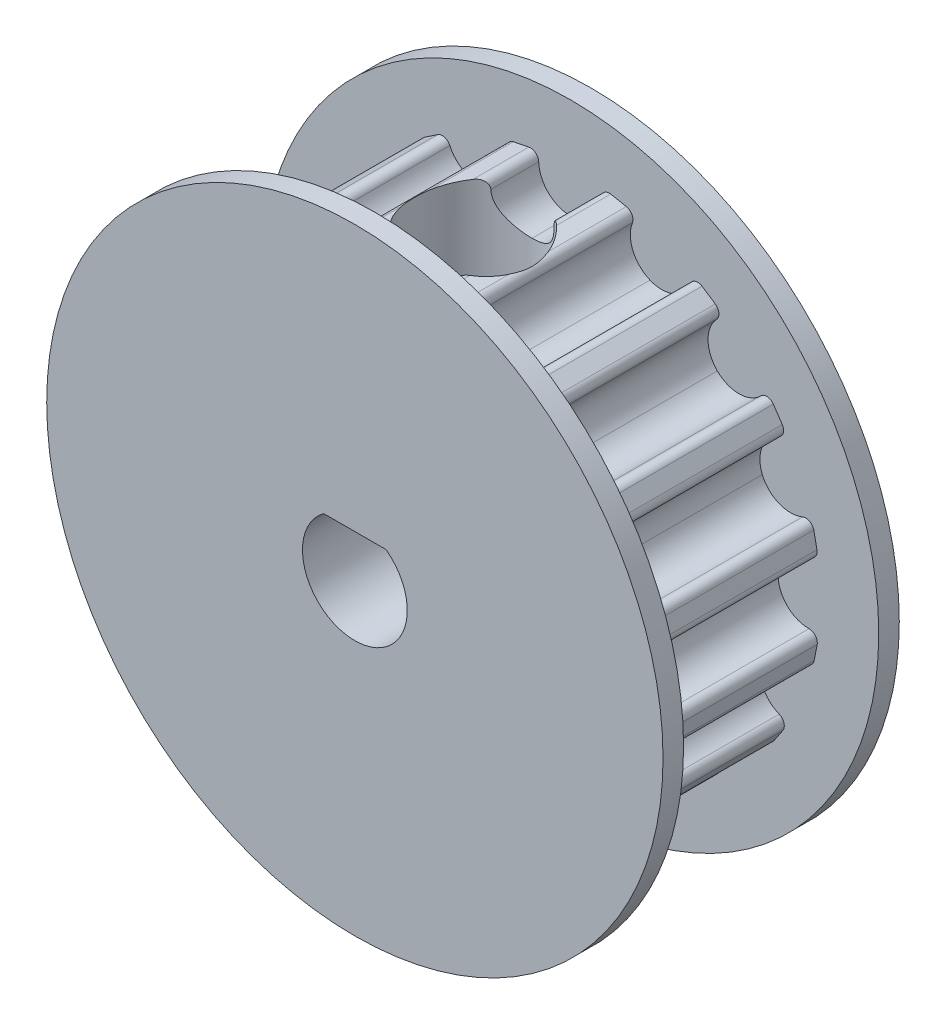
SolidWorks part; units mm, degrees
ref_plane "Front Plane" through (0, 0, 0) normal (1, 0, 0) x (0, 1, 0)
ref_plane "Top Plane" through (0, 0, 0) normal (0, 0, 1) x (0, 1, 0)
ref_plane "Right Plane" through (0, 0, 0) normal (0, 1, 0) x (-1, 0, 0)
sketch "Pulley Profile" plane through (0, 0, 0) normal (0, 0, 1) x (0, 1, 0)
  line L0 (0, 0) -> (0, 160.2939) construction
  line L1 (0, 0) -> (61.3418, 148.0922) construction
  line L2 (1.9542, 12.0044) -> (2.7129, 11.856)
  line L3 (1.8899, 11.6096) -> (2.6361, 11.4636) construction
  line L4 (6.3993, 10.3428) -> (7.0435, 9.9153)
  line L5 (9.8702, 7.1066) -> (10.3017, 6.4651)
  line L6 (11.8384, 2.7884) -> (11.9917, 2.0307)
  line L7 (12.0044, -1.9542) -> (11.856, -2.7129)
  line L8 (10.3428, -6.3993) -> (9.9153, -7.0435)
  line L9 (7.1066, -9.8702) -> (6.4651, -10.3017)
  line L10 (2.7884, -11.8384) -> (2.0307, -11.9917)
  line L11 (-1.9542, -12.0044) -> (-2.7129, -11.856)
  line L12 (-6.3993, -10.3428) -> (-7.0435, -9.9153)
  line L13 (-9.8702, -7.1066) -> (-10.3017, -6.4651)
  line L14 (-11.8384, -2.7884) -> (-11.9917, -2.0307)
  line L15 (-12.0044, 1.9542) -> (-11.856, 2.7129)
  line L16 (-10.3428, 6.3993) -> (-9.9153, 7.0435)
  line L17 (-7.1066, 9.8702) -> (-6.4651, 10.3017)
  line L18 (-2.7884, 11.8384) -> (-2.0307, 11.9917)
  circle A0 centre (0, 0) radius 10.1024 construction
  circle A1 centre (0, 0) radius 12.1624 construction
  arc A6 (0, 10.1024) -> (1.4899, 11.6059) centre (0, 11.5924) ccw
  arc A7 (1.4899, 11.6059) -> (1.9542, 12.0044) centre (1.8899, 11.6096) cw
  arc A8 (2.7129, 11.856) -> (3.0097, 11.3211) centre (2.6361, 11.4636) cw
  arc A9 (3.0097, 11.3211) -> (3.866, 9.3334) centre (4.4601, 10.7677) ccw
  circle A10 centre (0, 0) radius 12.7324 construction
  arc A11 (3.866, 9.3334) -> (5.8179, 10.1523) centre (4.4362, 10.71) ccw
  arc A12 (5.8179, 10.1523) -> (6.3993, 10.3428) centre (6.1889, 10.0026) cw
  arc A13 (7.0435, 9.9153) -> (7.113, 9.3076) centre (6.8224, 9.5822) cw
  arc A14 (7.113, 9.3076) -> (7.1435, 7.1435) centre (8.2412, 8.2412) ccw
  arc A15 (7.1435, 7.1435) -> (9.2602, 7.1531) centre (8.1971, 8.1971) ccw
  arc A16 (9.2602, 7.1531) -> (9.8702, 7.1066) centre (9.5456, 6.8728) cw
  arc A17 (10.3017, 6.4651) -> (10.1334, 5.8771) centre (9.97, 6.242) cw
  arc A18 (10.1334, 5.8771) -> (9.3334, 3.866) centre (10.7677, 4.4601) ccw
  arc A19 (9.3334, 3.866) -> (11.2927, 3.0649) centre (10.71, 4.4362) ccw
  arc A20 (11.2927, 3.0649) -> (11.8384, 2.7884) centre (11.4491, 2.6967) cw
  arc A21 (11.9917, 2.0307) -> (11.6111, 1.5518) centre (11.5998, 1.9515) cw
  arc A22 (11.6111, 1.5518) -> (10.1024, 0) centre (11.6548, 0) ccw
  arc A23 (10.1024, 0) -> (11.6059, -1.4899) centre (11.5924, 0) ccw
  arc A24 (11.6059, -1.4899) -> (12.0044, -1.9542) centre (11.6096, -1.8899) cw
  arc A25 (11.856, -2.7129) -> (11.3211, -3.0097) centre (11.4636, -2.6361) cw
  arc A26 (11.3211, -3.0097) -> (9.3334, -3.866) centre (10.7677, -4.4601) ccw
  arc A27 (9.3334, -3.866) -> (10.1523, -5.8179) centre (10.71, -4.4362) ccw
  arc A28 (10.1523, -5.8179) -> (10.3428, -6.3993) centre (10.0026, -6.1889) cw
  arc A29 (9.9153, -7.0435) -> (9.3076, -7.113) centre (9.5822, -6.8224) cw
  arc A30 (9.3076, -7.113) -> (7.1435, -7.1435) centre (8.2412, -8.2412) ccw
  arc A31 (7.1435, -7.1435) -> (7.1531, -9.2602) centre (8.1971, -8.1971) ccw
  arc A32 (7.1531, -9.2602) -> (7.1066, -9.8702) centre (6.8728, -9.5456) cw
  arc A33 (6.4651, -10.3017) -> (5.8771, -10.1334) centre (6.242, -9.97) cw
  arc A34 (5.8771, -10.1334) -> (3.866, -9.3334) centre (4.4601, -10.7677) ccw
  arc A35 (3.866, -9.3334) -> (3.0649, -11.2927) centre (4.4362, -10.71) ccw
  arc A36 (3.0649, -11.2927) -> (2.7884, -11.8384) centre (2.6967, -11.4491) cw
  arc A37 (2.0307, -11.9917) -> (1.5518, -11.6111) centre (1.9515, -11.5998) cw
  arc A38 (1.5518, -11.6111) -> (0, -10.1024) centre (0, -11.6548) ccw
  arc A39 (0, -10.1024) -> (-1.4899, -11.6059) centre (0, -11.5924) ccw
  arc A40 (-1.4899, -11.6059) -> (-1.9542, -12.0044) centre (-1.8899, -11.6096) cw
  arc A41 (-2.7129, -11.856) -> (-3.0097, -11.3211) centre (-2.6361, -11.4636) cw
  arc A42 (-3.0097, -11.3211) -> (-3.866, -9.3334) centre (-4.4601, -10.7677) ccw
  arc A43 (-3.866, -9.3334) -> (-5.8179, -10.1523) centre (-4.4362, -10.71) ccw
  arc A44 (-5.8179, -10.1523) -> (-6.3993, -10.3428) centre (-6.1889, -10.0026) cw
  arc A45 (-7.0435, -9.9153) -> (-7.113, -9.3076) centre (-6.8224, -9.5822) cw
  arc A46 (-7.113, -9.3076) -> (-7.1435, -7.1435) centre (-8.2412, -8.2412) ccw
  arc A47 (-7.1435, -7.1435) -> (-9.2602, -7.1531) centre (-8.1971, -8.1971) ccw
  arc A48 (-9.2602, -7.1531) -> (-9.8702, -7.1066) centre (-9.5456, -6.8728) cw
  arc A49 (-10.3017, -6.4651) -> (-10.1334, -5.8771) centre (-9.97, -6.242) cw
  arc A50 (-10.1334, -5.8771) -> (-9.3334, -3.866) centre (-10.7677, -4.4601) ccw
  arc A51 (-9.3334, -3.866) -> (-11.2927, -3.0649) centre (-10.71, -4.4362) ccw
  arc A52 (-11.2927, -3.0649) -> (-11.8384, -2.7884) centre (-11.4491, -2.6967) cw
  arc A53 (-11.9917, -2.0307) -> (-11.6111, -1.5518) centre (-11.5998, -1.9515) cw
  arc A54 (-11.6111, -1.5518) -> (-10.1024, 0) centre (-11.6548, 0) ccw
  arc A55 (-10.1024, 0) -> (-11.6059, 1.4899) centre (-11.5924, 0) ccw
  arc A56 (-11.6059, 1.4899) -> (-12.0044, 1.9542) centre (-11.6096, 1.8899) cw
  arc A57 (-11.856, 2.7129) -> (-11.3211, 3.0097) centre (-11.4636, 2.6361) cw
  arc A58 (-11.3211, 3.0097) -> (-9.3334, 3.866) centre (-10.7677, 4.4601) ccw
  arc A59 (-9.3334, 3.866) -> (-10.1523, 5.8179) centre (-10.71, 4.4362) ccw
  arc A60 (-10.1523, 5.8179) -> (-10.3428, 6.3993) centre (-10.0026, 6.1889) cw
  arc A61 (-9.9153, 7.0435) -> (-9.3076, 7.113) centre (-9.5822, 6.8224) cw
  arc A62 (-9.3076, 7.113) -> (-7.1435, 7.1435) centre (-8.2412, 8.2412) ccw
  arc A63 (-7.1435, 7.1435) -> (-7.1531, 9.2602) centre (-8.1971, 8.1971) ccw
  arc A64 (-7.1531, 9.2602) -> (-7.1066, 9.8702) centre (-6.8728, 9.5456) cw
  arc A65 (-6.4651, 10.3017) -> (-5.8771, 10.1334) centre (-6.242, 9.97) cw
  arc A66 (-5.8771, 10.1334) -> (-3.866, 9.3334) centre (-4.4601, 10.7677) ccw
  arc A67 (-3.866, 9.3334) -> (-3.0649, 11.2927) centre (-4.4362, 10.71) ccw
  arc A68 (-3.0649, 11.2927) -> (-2.7884, 11.8384) centre (-2.6967, 11.4491) cw
  arc A69 (-2.0307, 11.9917) -> (-1.5518, 11.6111) centre (-1.9515, 11.5998) cw
  arc A70 (-1.5518, 11.6111) -> (0, 10.1024) centre (0, 11.6548) ccw
  point P16 (0, 12.1624)
  point P18 (0, 12.7324)
  point P170 (0, 0)
  dimension "D1" = 25.4648
  dimension "D2" = 20.2048
  dimension "D3" = 24.3248
  dimension "D5" = 1.49
  dimension "D6" = 0.4
  dimension "D4" = 22.5
  dimension "D7" = 16
extrude "Pulley Profile Extrusion" add sketch "Pulley Profile" along normal blind 4.75 and the other way blind 4.75
sketch "Pulley Flange Sketch" plane through (0, 0, 4.75) normal (0, 0, 1) x (1, 0, 0)
  circle A0 centre (0, 0) radius 15
  dimension "D1" = 30
extrude "Pulley Flange Extrusion" add sketch "Pulley Flange Sketch" along normal blind 1
mirror "Flange Mirror" about plane through (0, 0, 0) normal (0, 0, 1) of "Pulley Flange Extrusion"
sketch "D-Shaft Sketch" plane through (0, 0, -5.75) normal (0, 0, -1) x (1, 0, 0)
  line L0 (-1.5166, -2.05) -> (1.5166, -2.05)
  arc A1 (-1.5166, -2.05) -> (1.5166, -2.05) centre (0, 0) cw
  dimension "D1" = 2.55
  dimension "D2" = 2.05
extrude "D-Shaft Cut" cut sketch "D-Shaft Sketch" against normal through all
ref_plane "Grub Screw Plane" through (0, 10.1024, 0) normal (0, -1, 0) x (-1, 0, 0)
sketch "3mm Bolt Head Sketch" plane through (0, 10.1024, 0) normal (0, -1, 0) x (-1, 0, 0)
  line L0 (0, 4.75) -> (0, -4.75) construction
  circle A0 centre (0, 0) radius 2.875
  dimension "D1" = 5.75
extrude "3mm Bolt Head Hole" cut sketch "3mm Bolt Head Sketch" against normal through all and the other way blind 3.1
sketch "Heat Set Insert Sketch" plane through (0, 7.0024, 0) normal (0, 1, 0) x (-1, 0, 0)
  circle A0 centre (0, 0) radius 2.3
  dimension "D1" = 4.6
extrude "3mm Heat Set Insert Hole" cut sketch "Heat Set Insert Sketch" against normal blind 4
sketch "Bolt Shaft Sketch" plane through (0, 3.0024, 0) normal (0, 1, 0) x (-1, 0, 0)
  circle A0 centre (0, 0) radius 1.75
  dimension "D1" = 3.5
extrude "3mm Bolt Shaft Hole" cut sketch "Bolt Shaft Sketch" against normal up to next
equation "\"pitch_diameter\"= ( ( 5mm * \"teeth_count\" ) / pi )"
equation "\"teeth_count\"= 16"
equation "\"root_diameter\"= \"outside_diameter\" - ( 2 * 2.06mm )"
equation "\"outside_diameter\"= \"pitch_diameter\" - 1.14mm"
equation "\"D1@Pulley Profile\" = \"pitch_diameter\""
equation "\"D2@Pulley Profile\" = \"root_diameter\""
equation "\"D3@Pulley Profile\" = \"outside_diameter\""
equation "\"pitch_angle\"= 360deg / \"teeth_count\""
equation "\"D4@Pulley Profile\" = \"pitch_angle\""
